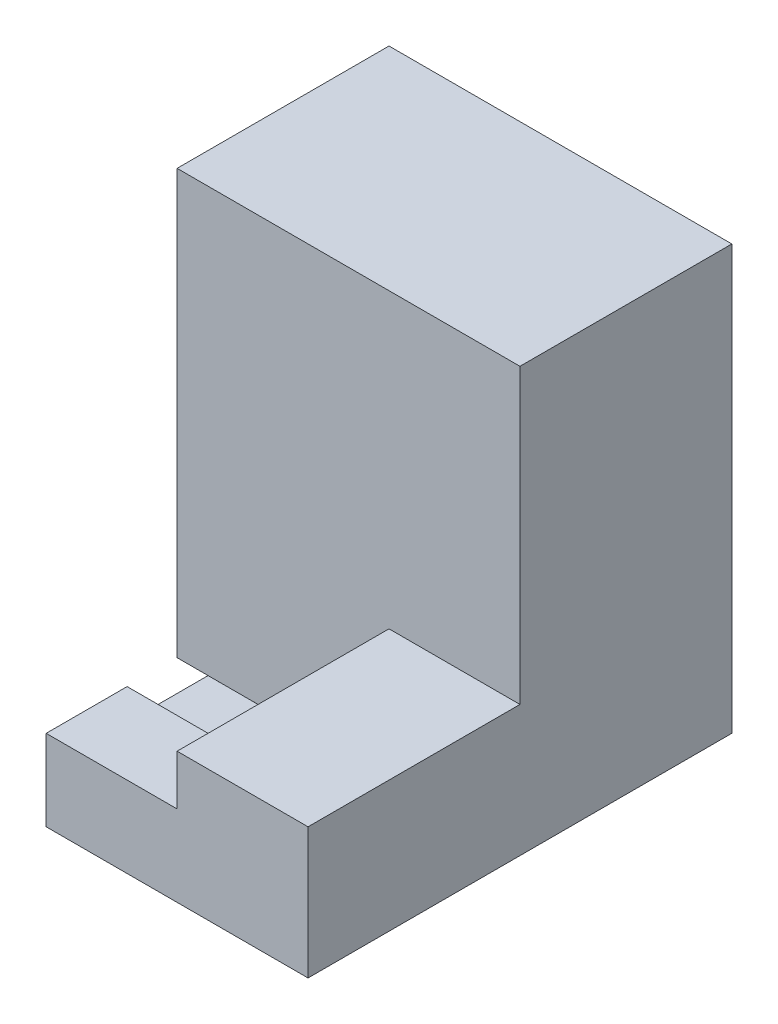
SolidWorks part; units mm, degrees
ref_plane "Front Plane" through (0, 0, 0) normal (0, 0, 1) x (1, 0, 0)
ref_plane "Top Plane" through (0, 0, 0) normal (0, 1, 0) x (1, 0, 0)
ref_plane "Right Plane" through (0, 0, 0) normal (1, 0, 0) x (0, 0, -1)
sketch "Sketch1" plane through (0, 0, 0) normal (0, 1, 0) x (1, 0, 0)
  line L0 (0, 0) -> (1, 0)
  line L1 (1, 0) -> (1, 1)
  line L2 (1, 1) -> (-1, 1)
  line L3 (-1, 1) -> (-1, -2)
  line L4 (-1, -2) -> (4, -2)
  line L5 (4, -2) -> (4, 6)
  line L6 (4, 6) -> (-9, 6)
  line L7 (-9, 6) -> (-9, -15)
  line L8 (-9, -15) -> (25, -15)
  line L9 (25, -15) -> (25, 40)
  line L10 (25, 40) -> (-64, 40)
  line L14 (0, 0) -> (1, 0)
  line L15 (0, 0) -> (0, -0.9972)
  line L16 (0, -0.9972) -> (1, -0.9972)
  line L17 (1, 0) -> (1, -0.9972)
  line L18 (1, 1) -> (2.0013, 1)
  line L19 (1, 1) -> (1, -0.9972)
  line L20 (1, -0.9972) -> (2.0013, -0.9972)
  line L21 (2.0013, 1) -> (2.0013, -0.9972)
  line L22 (-1, 1) -> (2.0013, 1)
  line L23 (-1, 1) -> (-1, 2.9977)
  line L24 (-1, 2.9977) -> (2.0013, 2.9977)
  line L25 (2.0013, 1) -> (2.0013, 2.9977)
  line L26 (-1, 2.9977) -> (-3.9997, 2.9977)
  line L27 (-1, 2.9977) -> (-1, -2)
  line L28 (-1, -2) -> (-3.9997, -2)
  line L29 (-3.9997, 2.9977) -> (-3.9997, -2)
  line L30 (-3.9997, -2) -> (4, -2)
  line L31 (-3.9997, -2) -> (-3.9997, -6.9969)
  line L32 (-3.9997, -6.9969) -> (4, -6.9969)
  line L33 (4, -2) -> (4, -6.9969)
  line L34 (4, -6.9969) -> (12.0032, -6.9969)
  line L35 (4, -6.9969) -> (4, 6)
  line L36 (4, 6) -> (12.0032, 6)
  line L37 (12.0032, -6.9969) -> (12.0032, 6)
  line L38 (12.0032, 6) -> (-9, 6)
  line L39 (12.0032, 6) -> (12.0032, 18.9956)
  line L40 (12.0032, 18.9956) -> (-9, 18.9956)
  line L41 (-9, 6) -> (-9, 18.9956)
  line L42 (-9, 18.9956) -> (-30.0001, 18.9956)
  line L43 (-9, 18.9956) -> (-9, -15)
  line L44 (-9, -15) -> (-30.0001, -15)
  line L45 (-30.0001, 18.9956) -> (-30.0001, -15)
  line L46 (-30.0001, -15) -> (25, -15)
  line L47 (-30.0001, -15) -> (-30.0001, -49.0049)
  line L48 (-30.0001, -49.0049) -> (25, -49.0049)
  line L49 (25, -15) -> (25, -49.0049)
  line L50 (25, -49.0049) -> (79.9988, -49.0049)
  line L51 (25, -49.0049) -> (25, 40)
  line L52 (25, 40) -> (79.9988, 40)
  line L53 (79.9988, -49.0049) -> (79.9988, 40)
  line L54 (79.9988, 40) -> (-64, 40)
  line L55 (79.9988, 40) -> (79.9988, 128.9961)
  line L56 (79.9988, 128.9961) -> (-64, 128.9961)
  line L57 (-64, 40) -> (-64, 128.9961)
  dimension "D1" = 1
  dimension "D2" = 1
  dimension "D3" = 2
  dimension "D4" = 3
  dimension "D5" = 5
  dimension "D6" = 8
  dimension "D7" = 13
  dimension "D8" = 21
  dimension "D9" = 34
  dimension "D10" = 55
  dimension "D11" = 89
  dimension "D13" = 178.001
extrude "Boss-Extrude1" add sketch "Sketch1" along normal blind 1 contours L21 L18 L1 L17 L20 | L15 L14 L17 L16 region at (1.5006, 0, -0.0014)
extrude "Boss-Extrude2" add sketch "Sketch1<3>" along normal blind 2 contours L18 L25 L24 L23 L2 region at (0.5006, 0, -1.9988)
sketch "Sketch1<3>" plane through (0, 0, 0) normal (0, 1, 0) x (1, 0, 0) same geometry as "Sketch1"
extrude "Boss-Extrude3" add sketch "Sketch1<4>" along normal blind 3 contours L26 L29 L28 L3 L23 region at (-2.4999, 0, -0.4988)
sketch "Sketch1<4>" plane through (0, 0, 0) normal (0, 1, 0) x (1, 0, 0) same geometry as "Sketch1"
extrude "Boss-Extrude4" add sketch "Sketch1<5>" along normal blind 5 contours L33 L4 L28 L31 L32 region at (0.0001, 0, 4.4985)
sketch "Sketch1<5>" plane through (0, 0, 0) normal (0, 1, 0) x (1, 0, 0) same geometry as "Sketch1"
extrude "Boss-Extrude5" add sketch "Sketch1<6>" along normal blind 8 contours L34 L37 L36 L5 L33 region at (8.0016, 0, 0.4985)
sketch "Sketch1<6>" plane through (0, 0, 0) normal (0, 1, 0) x (1, 0, 0) same geometry as "Sketch1"
extrude "Boss-Extrude6" add sketch "Sketch1<7>" along normal blind 13 contours L41 L6 L36 L39 L40 region at (1.5016, 0, -12.4978)
sketch "Sketch1<7>" plane through (0, 0, 0) normal (0, 1, 0) x (1, 0, 0) same geometry as "Sketch1"
extrude "Boss-Extrude7" add sketch "Sketch1<8>" along normal blind 21 contours L42 L45 L44 L7 L41 region at (-19.5, 0, -1.9978)
sketch "Sketch1<8>" plane through (0, 0, 0) normal (0, 1, 0) x (1, 0, 0) same geometry as "Sketch1"
extrude "Boss-Extrude8" add sketch "Sketch1<9>" along normal blind 34 contours L49 L8 L44 L47 L48 region at (-2.5, 0, 32.0025)
sketch "Sketch1<9>" plane through (0, 0, 0) normal (0, 1, 0) x (1, 0, 0) same geometry as "Sketch1"
extrude "Boss-Extrude9" add sketch "Sketch1<10>" along normal blind 55 contours L50 L53 L52 L9 L49 region at (52.4994, 0, 4.5025)
sketch "Sketch1<10>" plane through (0, 0, 0) normal (0, 1, 0) x (1, 0, 0) same geometry as "Sketch1"
extrude "Boss-Extrude10" add sketch "Sketch1<12>" along normal blind 178 contours L57 L10 L52 L55 L56 region at (7.9994, 0, -84.498)
sketch "Sketch1<12>" plane through (0, 0, 0) normal (0, 1, 0) x (1, 0, 0) same geometry as "Sketch1"
